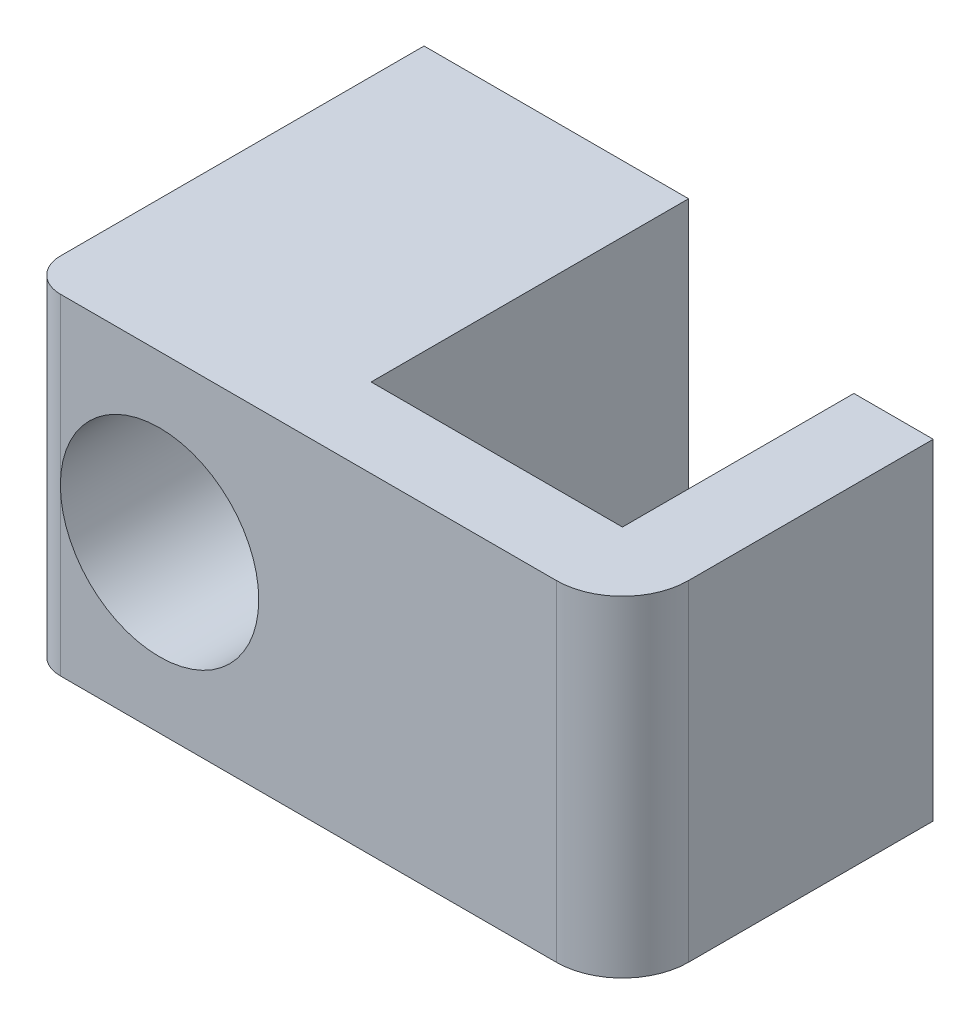
SolidWorks part; units mm, degrees
material "ABS"
ref_plane "前视基准面" through (0, 0, 0) normal (0, 0, 1) x (1, 0, 0)
ref_plane "上视基准面" through (0, 0, 0) normal (0, 1, 0) x (1, 0, 0)
ref_plane "右视基准面" through (0, 0, 0) normal (1, 0, 0) x (0, 0, -1)
sketch "草图1" plane through (0, 0, 0) normal (0, 0, 1) x (1, 0, 0)
  line L1 (-2, -2.5) -> (2, -2.5)
  line L2 (-2, -2.5) -> (-2, 2.5)
  line L3 (-2, 2.5) -> (2, 2.5)
  line L4 (2, -2.5) -> (2, 2.5)
  line L5 (-2, -2.5) -> (2, 2.5) construction
  line L6 (-2, 2.5) -> (2, -2.5) construction
  point P0 (0, 0)
  dimension "D1" = 5
  dimension "D2" = 4
extrude "凸台-拉伸1" add sketch "草图1" along normal blind 6
sketch "草图4" plane through (2, 0, 0) normal (1, 0, 0) x (0, 0, -1)
  line L0 (-4.8, 2.5) -> (-4.8, -2.5)
  line L1 (-6, 2.5) -> (0, 2.5) construction
  line L2 (-6, -2.5) -> (0, -2.5) construction
  line L3 (-4.8, -2.5) -> (-6, -2.5)
  line L4 (-6, -2.5) -> (-6, 2.5)
  line L5 (-6, 2.5) -> (-4.8, 2.5)
  dimension "D1" = 1.2
extrude "凸台-拉伸2" add sketch "草图4" along normal blind 5
sketch "草图5" plane through (0, 0, 4.8) normal (0, 0, -1) x (-1, 0, 0)
  line L0 (-7, 2.5) -> (-5.8, 2.5)
  line L1 (-7, 2.5) -> (-2, 2.5) construction
  line L2 (-5.8, 2.5) -> (-5.8, -2.5)
  line L3 (-7, -2.5) -> (-2, -2.5) construction
  line L4 (-5.8, -2.5) -> (-7, -2.5)
  line L5 (-7, -2.5) -> (-7, 2.5)
  dimension "D1" = 1.2
extrude "凸台-拉伸3" add sketch "草图5" along normal blind 3.5
fillet "圆角1" radius 1 1 edges at (7, 0, 6)
sketch "草图6" plane through (0, 0, 6) normal (0, 0, 1) x (1, 0, 0)
  line L0 (2, -2.5) -> (2, 2.5) construction
  line L1 (-2, -2.5) -> (6, -2.5) construction
  line L2 (6, 2.5) -> (-2, 2.5) construction
  line L3 (-2, 2.5) -> (-2, -2.5) construction
  line L4 (-2, 2.5) -> (2, -2.5) construction
  line L5 (-2, -2.5) -> (2, 2.5) construction
  circle A0 centre (0, 0) radius 1.5
  dimension "D1" = 4
extrude "切除-拉伸1" cut sketch "草图6" against normal through all
fillet "圆角2" radius 0.5 1 edges at (-2, 0, 6)
